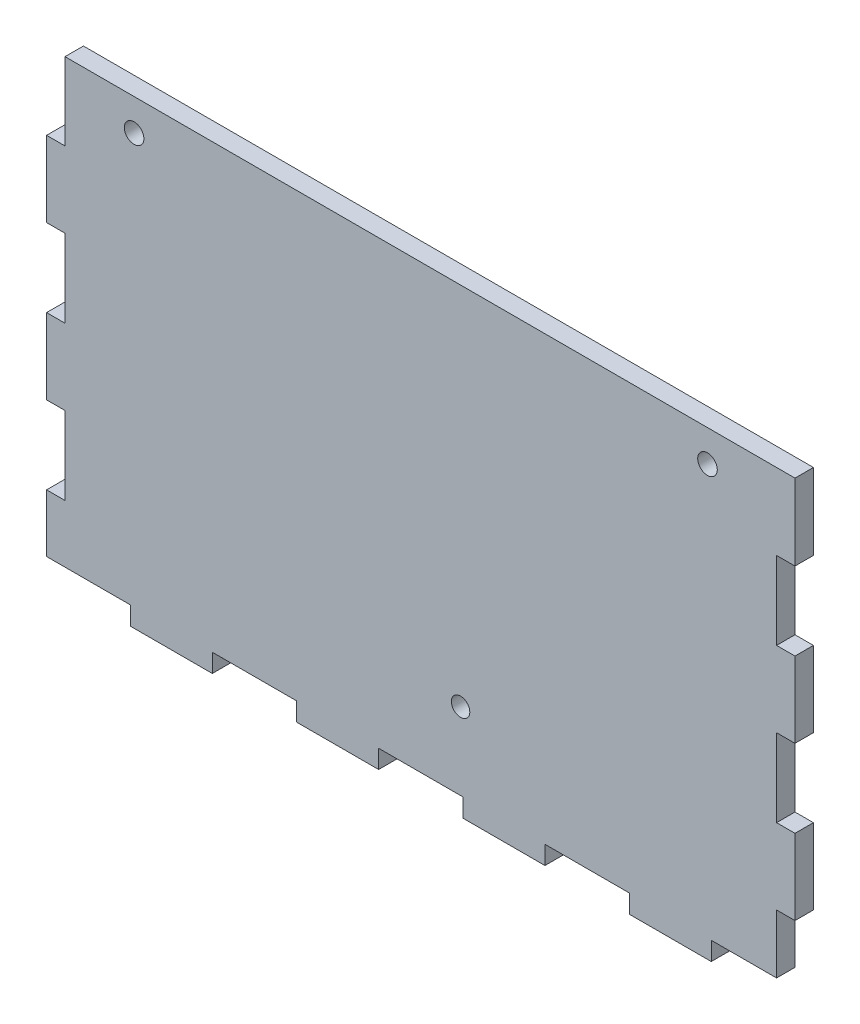
SolidWorks part; units mm, degrees
material "Acrylic (Medium-high impact)"
ref_plane "Front Plane" through (0, 0, 0) normal (0, 0, 1) x (1, 0, 0)
ref_plane "Top Plane" through (0, 0, 0) normal (0, 1, 0) x (1, 0, 0)
ref_plane "Right Plane" through (0, 0, 0) normal (1, 0, 0) x (0, 0, -1)
sketch "Sketch1" plane through (0, 0, 0) normal (0, 0, 1) x (1, 0, 0)
  line L1 (0, 0) -> (130, 0)
  line L2 (0, 0) -> (0, 80)
  line L3 (0, 80) -> (130, 80)
  line L4 (130, 0) -> (130, 80)
  dimension "D1" = 130
  dimension "D2" = 80
extrude "Boss-Extrude1" add sketch "Sketch1" along normal blind 3.2
sketch "Sketch2" plane through (0, 0, 3.2) normal (0, 0, 1) x (1, 0, 0)
  line L61 (14.4444, 3.2) -> (28.8889, 3.2) construction
  line L62 (0, 0) -> (14.4444, 0)
  line L67 (0, 0) -> (0, 3.2)
  line L72 (0, 3.2) -> (14.4444, 3.2)
  line L77 (14.4444, 0) -> (14.4444, 3.2)
  line L97 (28.8889, 0) -> (28.8889, 3.2)
  line L98 (28.8889, 0) -> (43.3333, 0)
  line L107 (43.3333, 0) -> (43.3333, 3.2)
  line L115 (28.8889, 3.2) -> (43.3333, 3.2)
  line L117 (43.3333, 3.2) -> (57.7778, 3.2) construction
  line L123 (57.7778, 0) -> (57.7778, 3.2)
  line L128 (57.7778, 0) -> (72.2222, 0)
  line L129 (72.2222, 0) -> (72.2222, 3.2)
  line L131 (57.7778, 3.2) -> (72.2222, 3.2)
  line L132 (72.2222, 3.2) -> (86.6667, 3.2) construction
  line L133 (86.6667, 0) -> (86.6667, 3.2)
  line L134 (86.6667, 0) -> (101.1111, 0)
  line L135 (101.1111, 0) -> (101.1111, 3.2)
  line L136 (86.6667, 3.2) -> (101.1111, 3.2)
  line L137 (101.1111, 3.2) -> (115.5556, 3.2) construction
  line L138 (115.5556, 0) -> (115.5556, 3.2)
  line L139 (115.5556, 0) -> (130, 0)
  line L142 (130, 0) -> (130, 80) construction
  line L143 (0, 80) -> (0, 0) construction
  line L144 (0, 13.3333) -> (3.2, 13.3333)
  line L145 (0, 13.3333) -> (0, 26.6667)
  line L146 (130, 3.2) -> (144.4444, 3.2) construction
  line L147 (0, 26.6667) -> (3.2, 26.6667)
  line L148 (3.2, 13.3333) -> (3.2, 26.6667)
  line L149 (3.2, 13.3333) -> (3.2, 0) construction
  line L150 (0, 40) -> (0, 53.3333)
  line L151 (0, 40) -> (3.2, 40)
  line L152 (3.2, 40) -> (3.2, 53.3333)
  line L153 (0, 53.3333) -> (3.2, 53.3333)
  line L154 (3.2, 40) -> (3.2, 26.6667) construction
  line L155 (0, 66.6667) -> (0, 80)
  line L156 (0, 66.6667) -> (3.2, 66.6667)
  line L157 (3.2, 66.6667) -> (3.2, 80)
  line L158 (0, 80) -> (3.2, 80)
  line L159 (3.2, 66.6667) -> (3.2, 53.3333) construction
  line L160 (130, 80) -> (0, 80) construction
  line L161 (126.8, 80) -> (126.8, 66.6667) construction
  line L162 (126.8, 40) -> (126.8, 26.6667)
  line L163 (126.8, 66.6667) -> (130, 66.6667)
  line L164 (126.8, 66.6667) -> (126.8, 53.3333)
  line L165 (126.8, 53.3333) -> (130, 53.3333)
  line L166 (130, 66.6667) -> (130, 53.3333)
  line L167 (126.8, 40) -> (130, 40)
  line L168 (130, 40) -> (130, 26.6667)
  line L169 (126.8, 26.6667) -> (130, 26.6667)
  line L170 (126.8, 53.3333) -> (126.8, 40) construction
  line L172 (126.8, 13.3333) -> (130, 13.3333)
  line L173 (130, 13.3333) -> (130, 0)
  line L175 (126.8, 26.6667) -> (126.8, 13.3333) construction
  line L183 (115.5556, 3.2) -> (130, 3.2) [skipped]
  line L184 (130, 0) -> (130, 3.2) [skipped]
  line L185 (126.8, 13.3333) -> (126.8, 3.2)
  line L186 (126.8, 3.2) -> (115.5556, 3.2)
  line L187 (126.8, 0) -> (130, 0) [skipped]
  line L188 (126.8, 13.3333) -> (126.8, 0) [skipped]
  dimension "D2" = 3.2
  dimension "D4" = 3.2
  dimension "D6" = 3.2
  dimension "D1" = 5
  dimension "D3" = 3
  dimension "D5" = 3
extrude "Cut-Extrude1" cut sketch "Sketch2" against normal through all
sketch "Sketch3" plane through (0, 0, 3.2) normal (0, 0, 1) x (1, 0, 0)
  line L0 (0, 66.6667) -> (0, 53.3333) construction
  line L1 (130, 80) -> (3.2, 80) construction
  line L2 (0, 66.6667) -> (130, 66.6667) construction
  line L3 (65, 66.6667) -> (65, 50066.6667) construction
  circle A0 centre (15.2, 74.5) radius 1.7
  circle A1 centre (114.8, 74.5) radius 1.7
  point P10 (65, 66.6667)
  dimension "D1" = 3.4
  dimension "D2" = 15.2
  dimension "D3" = 5.5
extrude "Cut-Extrude2" cut sketch "Sketch3" against normal up to next
sketch "Sketch4" plane through (0, 0, 0) normal (0, 0, -1) x (-1, 0, 0)
  line L0 (-130, 13.3333) -> (-130, 26.6667) construction
  line L4 (-72.2222, 3.2) -> (-57.7778, 3.2) construction
  circle A0 centre (-71.91, 16.56) radius 1.6
  dimension "D2" = 3.2
  dimension "D1" = 58.09
  dimension "D3" = 13.36
extrude "Tuning driver hole" cut sketch "Sketch4" against normal up to next
other "Width tolerance" flip direction yes face at (128.4, 53.3333, 1.6) face at (128.4, 26.6667, 1.6) face at (128.4, 13.3333, 1.6) face at (128.4, 40, 1.6) face at (128.4, 66.6667, 1.6) face at (115.5556, 1.6, 1.6) face at (86.6667, 1.6, 1.6) face at (57.7778, 1.6, 1.6) face at (28.8889, 1.6, 1.6) face at (14.4444, 1.6, 1.6) face at (43.3333, 1.6, 1.6) face at (72.2222, 1.6, 1.6) face at (101.1111, 1.6, 1.6) face at (1.6, 26.6667, 1.6) face at (1.6, 13.3333, 1.6) face at (1.6, 40, 1.6) face at (1.6, 53.3333, 1.6) face at (1.6, 66.6667, 1.6) offset 0.1 parameters "D1"=0.1
equation "\"wall_thickness\"= 3.2mm"
equation "\"D1@Boss-Extrude1\"=\"wall_thickness\""
equation "\"slot_width_tolerance\"= 0.1mm"
equation "\"slot_depth\"= 3.2mm"
equation "\"D2@Sketch2\"=\"slot_depth\""
equation "\"D4@Sketch2\"=\"slot_depth\""
equation "\"D6@Sketch2\"=\"slot_depth\""
equation "\"D2@Sketch3\"=12.00mm+\"slot_depth\""
equation "\"D1@Width tolerance\"=\"slot_width_tolerance\""
